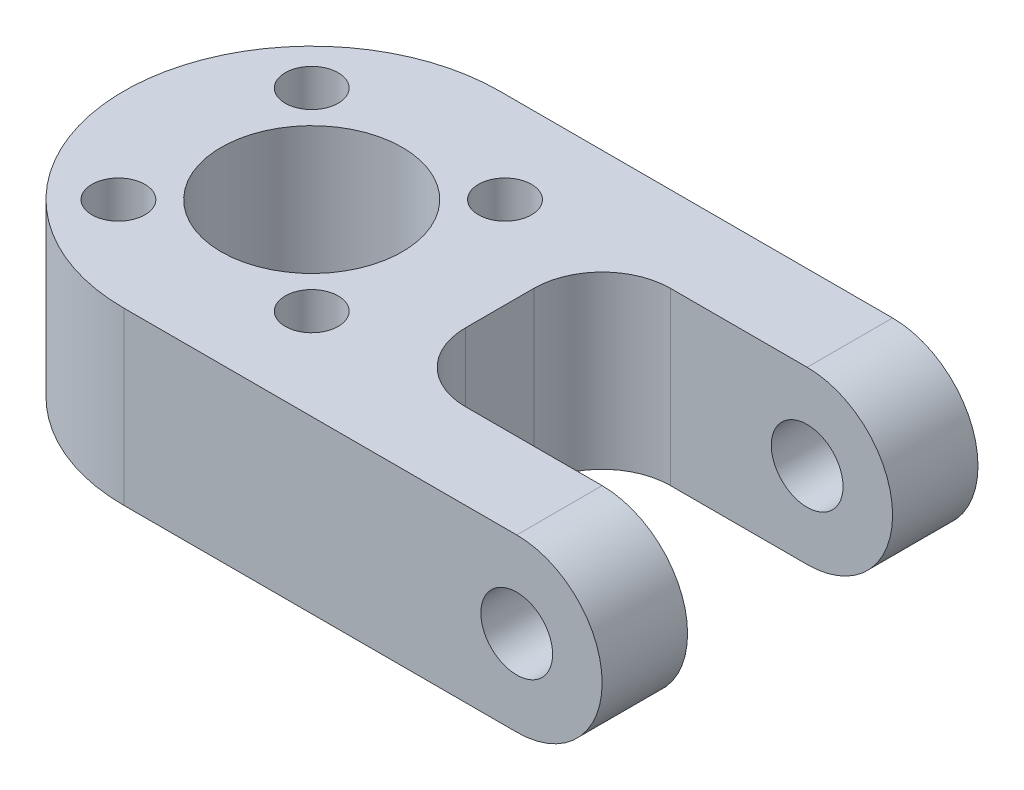
SolidWorks part; units mm, degrees
ref_plane "Front Plane" through (0, 0, 0) normal (0, 0, 1) x (1, 0, 0)
ref_plane "Top Plane" through (0, 0, 0) normal (0, 1, 0) x (1, 0, 0)
ref_plane "Right Plane" through (0, 0, 0) normal (1, 0, 0) x (0, 0, -1)
sketch "Sketch2" plane through (0, 0, 0) normal (0, 1, 0) x (1, 0, 0)
  line L5 (-22.3431, -5.6569) -> (-28, 0) construction
  line L8 (-28, 0) -> (-33.6569, -5.6569) construction
  line L10 (-33.6569, 5.6569) -> (-28, 0) construction
  line L11 (-22.3431, 5.6569) -> (-28, 0) construction
  line L13 (-22.3431, -5.6569) -> (-22.3431, 5.6569) construction
  line L16 (-28, -11) -> (0, -11)
  line L19 (-28, 11) -> (0, 11)
  line L20 (0, -11) -> (0, -6)
  line L21 (0, -6) -> (-17, -6)
  line L22 (-17, -6) -> (-17, 6)
  line L23 (-17, 6) -> (0, 6)
  line L24 (0, 6) -> (0, 11)
  circle A15 centre (-28, 0) radius 5.3
  circle A17 centre (-33.6569, 5.6569) radius 1.55
  circle A18 centre (-33.6569, -5.6569) radius 1.55
  circle A19 centre (-22.3431, 5.6569) radius 1.55
  circle A20 centre (-22.3431, -5.6569) radius 1.55
  arc A21 (-28, 11) -> (-28, -11) centre (-28, 0) ccw
  circle A22 centre (-28, 0) radius 8 construction
  dimension "D1" = 16
  dimension "D2" = 28
  dimension "D7" = 10.6
  dimension "D8" = 3.1
  dimension "D3" = 5
  dimension "D4" = 17
  dimension "D5" = 5
  dimension "D6" = 12
  dimension "D9" = 45
  dimension "D10" = 6
extrude "Boss-Extrude2" add sketch "Sketch2" along normal blind 10 contours A21 L16 L20 L21 L22 L23 L24 L19 | A15 | A18 | A20 | A19 | A17
sketch "Sketch7" plane through (0, 0, 11) normal (0, 0, 1) x (1, 0, 0)
  line L0 (0, 5) -> (-5, 5) construction
  line L1 (0, 10) -> (0, 0) construction
  line L2 (-5, 10) -> (0, 10)
  line L3 (0, 10) -> (0, 0)
  line L4 (0, 0) -> (-5, 0)
  circle A0 centre (-5, 5) radius 2.1
  circle A1 centre (-5, 5) radius 5
  line M3 (-28, 0) -> (0, 0)
  line M4 (0, 0) -> (0, 10)
  line M5 (0, 10) -> (-28, 10)
extrude "Cut-Extrude2" cut sketch "Sketch7" against normal through all contours A1 L3 M5 | A1 M3 M4 | A0 region at (-1.1168, 8.8832, 11) region at (-1.1168, 1.1168, 11) region at (-5, 5, 11)
fillet "Fillet1" radius 4 2 edges at (-17, 5, -6) (-17, 5, 6)
